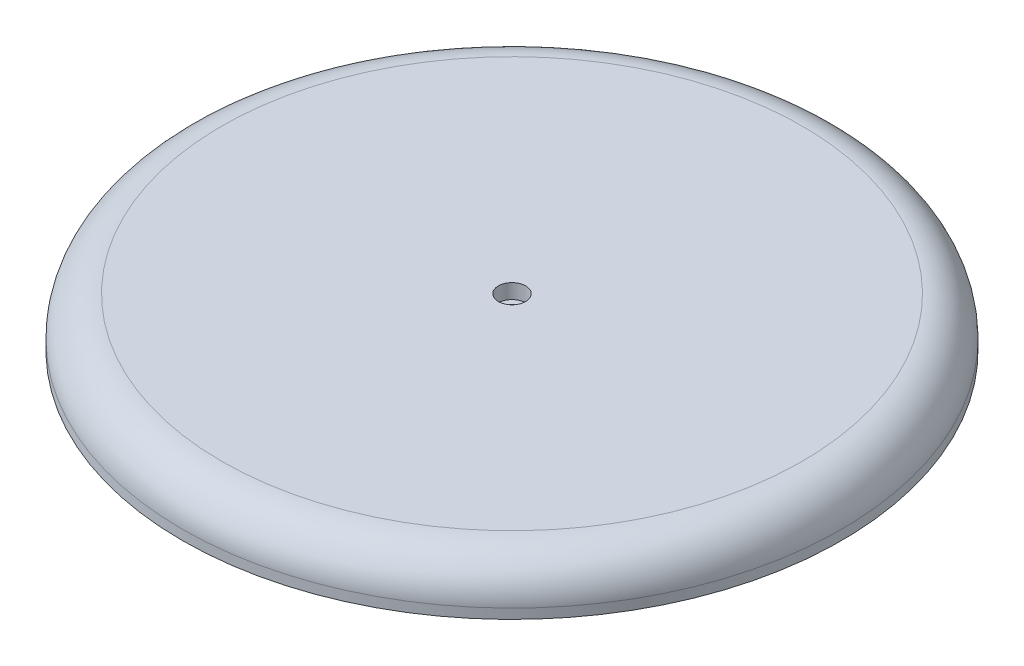
SolidWorks part; units mm, degrees
ref_plane "Front Plane" through (0, 0, 0) normal (0, 0, 1) x (1, 0, 0)
ref_plane "Top Plane" through (0, 0, 0) normal (0, 1, 0) x (1, 0, 0)
ref_plane "Right Plane" through (0, 0, 0) normal (1, 0, 0) x (0, 0, -1)
sketch "Sketch1" plane through (0, 0, 0) normal (0, 1, 0) x (1, 0, 0)
  circle A0 centre (0, 0) radius 67.15
  circle A1 centre (0, 0) radius 30.48
  dimension "D1" = 134.3
  dimension "D2" = 60.96
extrude "Boss-Extrude1" add sketch "Sketch1" along normal blind 10 contours A0
extrude "Boss-Extrude2" add sketch "Sketch1<3>" against normal blind 2 contours A1 region at (0, 0, 0)
sketch "Sketch1<3>" plane through (0, 0, 0) normal (0, 1, 0) x (1, 0, 0) same geometry as "Sketch1"
fillet "Fillet1" radius 8 1 edges at (0, 10, 67.15)
sketch "Sketch2" plane through (0, 10, 0) normal (0, 1, 0) x (1, 0, 0)
  circle A0 centre (0, 0) radius 2.775
  dimension "D1" = 5.55
extrude "Cut-Extrude1" cut sketch "Sketch2" against normal blind 3
sketch "Sketch3" plane through (0, 7, 0) normal (0, 1, 0) x (1, 0, 0)
  circle A0 centre (0, 0) radius 1.6
  dimension "D1" = 3.2
extrude "Cut-Extrude2" cut sketch "Sketch3" against normal up to next
